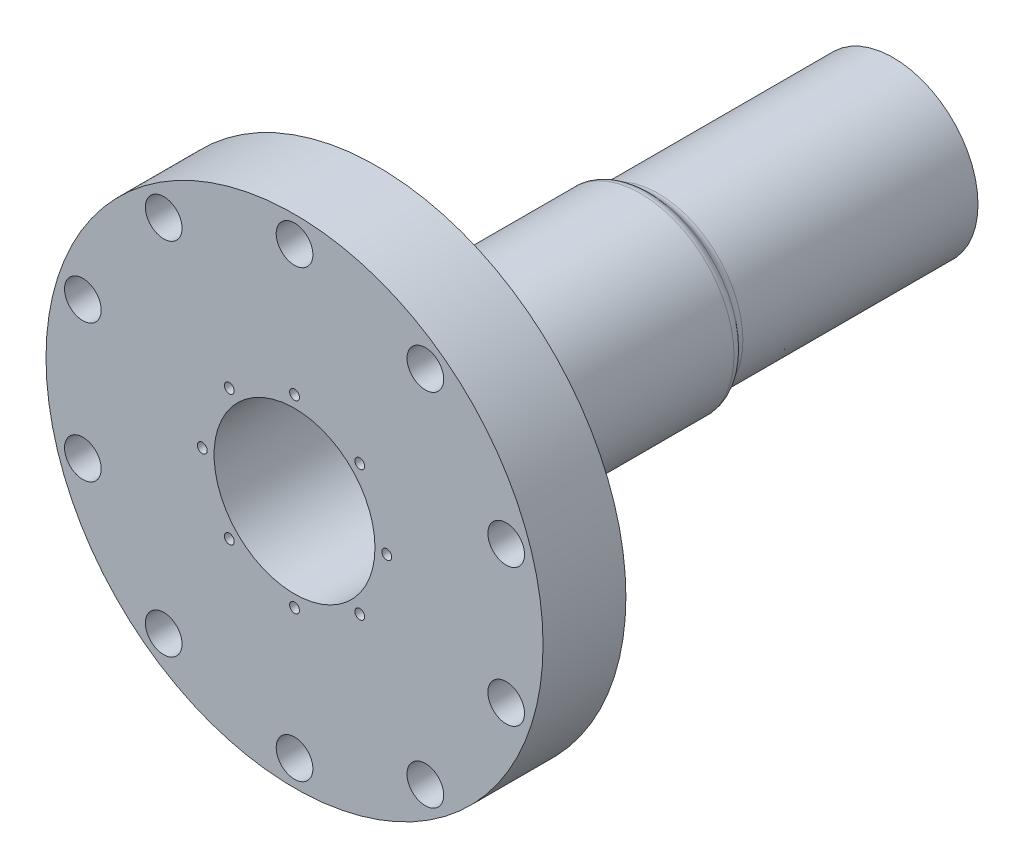
SolidWorks part; units mm, degrees
ref_plane "Front Plane" through (0, 0, 0) normal (0, 0, 1) x (1, 0, 0)
ref_plane "Top Plane" through (0, 0, 0) normal (0, 1, 0) x (1, 0, 0)
ref_plane "Right Plane" through (0, 0, 0) normal (1, 0, 0) x (0, 0, -1)
sketch "Sketch1" plane through (0, 0, 0) normal (0, 0, 1) x (1, 0, 0)
  circle A0 centre (0, 0) radius 18.5
  circle A1 centre (0, 0) radius 19.5
  dimension "D1" = 37
  dimension "D2" = 39
extrude "Extrude1" add sketch "Sketch1" against normal blind 137.668
sketch "Sketch4" plane through (0, 0, 0) normal (0, 0, 1) x (1, 0, 0)
  circle A0 centre (0, 0) radius 19.5
  circle A1 centre (0, 0) radius 57.15
  dimension "D1" = 114.3
extrude "Extrude2" add sketch "Sketch4" against normal blind 19.05
sketch "Sketch5" plane through (0, 0, 0) normal (0, 0, 1) x (1, 0, 0)
  circle A0 centre (0, 51.181) radius 4.2164
  dimension "D1" = 8.4328
  dimension "D2" = 51.181
extrude "Cut-Extrude1" cut sketch "Sketch5" against normal up to next
pattern_circular "CirPattern1" count 10 over 360 about axis through (0, 0, -137.668) along (0, 0, 1) of "Cut-Extrude1"
sketch "Sketch6" plane through (0, 0, 0) normal (0, 0, 1) x (1, 0, 0)
  line L0 (0, 0) -> (0, -32.2747) construction
  line L1 (0, 0) -> (34.1161, 0) construction
  point P4 (15, -15)
  point P5 (-15, -15)
  point P6 (-15, 15)
  point P7 (15, 15)
  dimension "D1" = 30
  dimension "D2" = 30
hole_wizard "#4-40 Tapped Hole2" positions "Sketch9" profile "Sketch8" tap size "#4-40" standard "Ansi Inch"
sketch "Sketch9" plane through (0, 0, 0) normal (0, 0, 1) x (1, 0, 0)
  line L0 (0, 0) -> (34.1161, 0) construction
  line L1 (0, 0) -> (0, -32.2747) construction
  line L2 (0, 21.2132) -> (-21.2132, 0) construction
  line L3 (-21.2132, 0) -> (0, -21.2132) construction
  point P1 (15, -15)
  point P4 (-15, -15)
  point P7 (-15, 15)
  point P10 (15, 15)
  point P13 (0, 21.2132)
  point P15 (-21.2132, 0)
  point P17 (21.2132, 0)
  point P21 (0, -21.2132)
  dimension "D1" = 30
  dimension "D2" = 30
  dimension "D3" = 30
  dimension "D4" = 30
  dimension "D5" = 30
  dimension "D6" = 30
  dimension "D7" = 90
sketch "Sketch8" plane through (15, -15, 0) normal (1, 0, 0) x (0, -1, 0)
  line L0 (0, 0) -> (0, 8.2992)
  line L1 (0, 8.2992) -> (1.1303, 7.62)
  line L2 (1.1303, 7.62) -> (1.1303, 0)
  line L5 (1.1303, 0) -> (0, 0)
  line L10 (0, 8.2992) -> (-1.1303, 7.62) construction
  line L11 (0, -6.35) -> (0, 107.95) construction
  dimension "Tap Drill Dia." = 2.2606
  dimension "Tap Drill Depth" = 7.62
  dimension "Drill Angle" = 118
cosmetic thread "Hole Thread5" parameters "D1"=5.588, "D2"=2.8448
cosmetic thread "Hole Thread6" parameters "D1"=5.588, "D2"=2.8448
cosmetic thread "Hole Thread7" parameters "D1"=5.588, "D2"=2.8448
cosmetic thread "Hole Thread8" parameters "D1"=5.588, "D2"=2.8448
cosmetic thread "Hole Thread9" parameters "D1"=5.588, "D2"=2.8448
cosmetic thread "Hole Thread10" parameters "D1"=5.588, "D2"=2.8448
cosmetic thread "Hole Thread11" parameters "D1"=5.588, "D2"=2.8448
cosmetic thread "Hole Thread12" parameters "D1"=5.588, "D2"=2.8448
sketch "Sketch10" plane through (0, 0, -137.668) normal (0, 0, -1) x (-1, 0, 0)
  circle A0 centre (0, 0) radius 19
  circle A1 centre (0, 0) radius 19.5 construction
  dimension "D1" = 0.5
extrude "Extrude3" cut sketch "Sketch10" against normal blind 25.4
sketch "Sketch12" plane through (0, 0, -19.05) normal (0, 0, -1) x (-1, 0, 0)
  circle A0 centre (0, 0) radius 21.5
  circle A1 centre (0, 0) radius 19
  dimension "D1" = 43
extrude "Extrude4" add sketch "Sketch12" along normal blind 63
fillet "Fillet1" radius 2.54 1 edges at (-21.5, 0, -82.05)
fillet "Fillet2" radius 2.54 1 edges at (-19.5, 0, -82.05)
